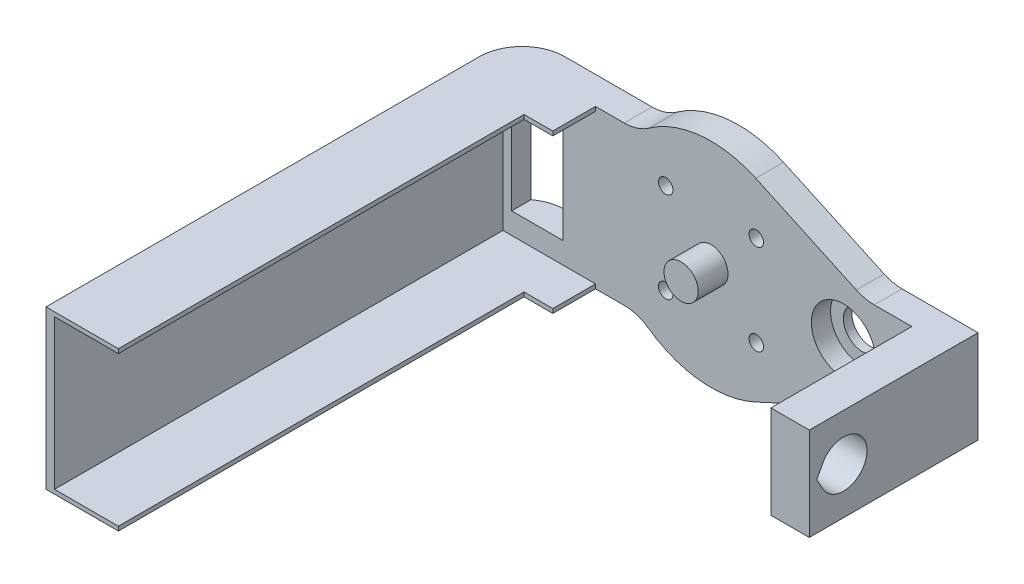
SolidWorks part; units mm, degrees
ref_plane "Front Plane" through (0, 0, 0) normal (0, 0, 1) x (1, 0, 0)
ref_plane "Top Plane" through (0, 0, 0) normal (0, 1, 0) x (1, 0, 0)
ref_plane "Right Plane" through (0, 0, 0) normal (1, 0, 0) x (0, 0, -1)
sketch "Sketch1" plane through (0, 0, 0) normal (0, 0, 1) x (1, 0, 0)
  line L0 (10.4839, 22.6956) -> (36.0323, 10.8939)
  line L1 (36.0323, -10.8939) -> (10.4839, -22.6956)
  circle A0 centre (0, 0) radius 22.215 construction
  circle A1 centre (31, 0) radius 10.2 construction
  arc A2 (10.4839, 22.6956) -> (10.4839, -22.6956) centre (0, 0) ccw
  arc A3 (36.0323, -10.8939) -> (36.0323, 10.8939) centre (31, 0) ccw
  dimension "D1" = 20.4
  dimension "D2" = 44.43
  dimension "D4" = 25
  dimension "D5" = 12
  dimension "D3" = 31
extrude "Boss-Extrude1" add sketch "Sketch1" along normal blind 4.5
sketch "Sketch2" plane through (0, 0, 4.5) normal (0, 0, 1) x (1, 0, 0)
  circle A0 centre (31, 0) radius 7.5
  dimension "D1" = 15
extrude "Cut-Extrude1" cut sketch "Sketch2" against normal through all
sketch "Sketch3" plane through (0, 0, 4.5) normal (0, 0, 1) x (1, 0, 0)
  circle A0 centre (0, 0) radius 4
  dimension "D1" = 8
extrude "Boss-Extrude2" add sketch "Sketch3" along normal blind 7
sketch "Sketch4" plane through (0, 0, 0) normal (0, 0, -1) x (-1, 0, 0)
  line L0 (-36.0323, 10.8939) -> (-56.0323, 10.8939)
  line L1 (-36.0323, -10.8939) -> (-56.0323, -10.8939)
  line L2 (-56.0323, -10.8939) -> (-56.0323, 10.8939)
  line L3 (22.5016, 10.8939) -> (42.5016, 10.8939)
  line L4 (42.5016, 10.8939) -> (42.5016, -10.8939)
  line L5 (42.5016, -10.8939) -> (22.5016, -10.8939)
  arc A0 (-10.4839, -22.6956) -> (-10.4839, 22.6956) centre (0, 0) ccw construction
  arc A1 (22.5016, -10.8939) -> (22.5016, 10.8939) centre (0, 0) ccw
  arc A2 (-36.0323, 10.8939) -> (-36.0323, -10.8939) centre (-31, 0) ccw construction
  arc A3 (-36.0323, 10.8939) -> (-36.0323, -10.8939) centre (-31, 0) ccw
  dimension "D1" = 20
  dimension "D2" = 20
extrude "Boss-Extrude3" add sketch "Sketch4" against normal up to surface (4.5 mm away) up to face at (4, 0, 4.5)
fillet "Fillet1" radius 10 4 edges at (-42.5016, 10.8939, 2.25) (-42.5016, -10.8939, 2.25) (56.0323, -10.8939, 2.25) (56.0323, 10.8939, 2.25)
sketch "Sketch8" plane through (0, 0, 4.5) normal (0, 0, 1) x (1, 0, 0)
  line L0 (56.0323, 0.8939) -> (56.0323, -0.8939) construction
  line L2 (56.0323, 0.8939) -> (56.0323, -0.8939)
  line L3 (55.4014, -4.3896) -> (55.4014, 4.3896)
  line L4 (-42.5016, -0.8939) -> (-42.5016, 0.8939) construction
  line L6 (-42.5016, -0.8939) -> (-42.5016, 0.8939)
  line L7 (-41.8707, 4.3896) -> (-41.8707, -4.3896)
  arc A0 (56.0323, 0.8939) -> (46.0323, 10.8939) centre (46.0323, 0.8939) ccw construction
  arc A1 (46.0323, -10.8939) -> (56.0323, -0.8939) centre (46.0323, -0.8939) ccw construction
  arc A2 (56.0323, 0.8939) -> (55.4014, 4.3896) centre (46.0323, 0.8939) ccw
  arc A3 (55.4014, -4.3896) -> (56.0323, -0.8939) centre (46.0323, -0.8939) ccw
  arc A4 (-32.5016, 10.8939) -> (-42.5016, 0.8939) centre (-32.5016, 0.8939) ccw construction
  arc A5 (-42.5016, -0.8939) -> (-32.5016, -10.8939) centre (-32.5016, -0.8939) ccw construction
  arc A6 (-41.8707, 4.3896) -> (-42.5016, 0.8939) centre (-32.5016, 0.8939) ccw
  arc A7 (-42.5016, -0.8939) -> (-41.8707, -4.3896) centre (-32.5016, -0.8939) ccw
extrude "Cut-Extrude4" cut sketch "Sketch8" against normal through all
sketch "Sketch9" plane through (0, 0, 4.5) normal (0, 0, 1) x (1, 0, 0)
  circle A0 centre (0, 0) radius 15 construction
  circle A1 centre (-10.6066, 10.6066) radius 1
  circle A2 centre (10.6066, 10.6066) radius 1
  circle A3 centre (10.6066, -10.6066) radius 1
  circle A4 centre (-10.6066, -10.6066) radius 1
  point P14 (0, 0)
  dimension "D1" = 30
  dimension "D2" = 2
  dimension "D3" = 4
extrude "Cut-Extrude5" cut sketch "Sketch9" against normal through all
sketch "Sketch10" plane through (0, 0, 4.5) normal (0, 0, 1) x (1, 0, 0)
  circle A0 centre (-10.6066, 10.6066) radius 1.7
  circle A1 centre (10.6066, 10.6066) radius 1.7
  circle A2 centre (10.6066, -10.6066) radius 1.7
  circle A3 centre (-10.6066, -10.6066) radius 1.7
  dimension "D1" = 3.4
extrude "Cut-Extrude6" cut sketch "Sketch10" against normal blind 2.4
sketch "Sketch11" plane through (0, 0, 0) normal (0, 0, -1) x (-1, 0, 0)
  line L0 (-40.9602, 14.6461) -> (-73.6718, 18.9155)
  line L1 (-73.6718, 18.9155) -> (-68.6403, -15.6759)
  line L2 (-68.6403, -15.6759) -> (-41.445, -13.2122)
  arc A0 (-40.9602, 14.6461) -> (-41.445, -13.2122) centre (0, 0) ccw
  dimension "D1" = 87
extrude "Cut-Extrude7" cut sketch "Sketch11" against normal up to surface (4.5 mm away) up to face at (-8.9066, -10.6066, 4.5)
fillet "Fillet2" radius 10 2 edges at (42.1138, -10.8939, 2.25) (42.1138, 10.8939, 2.25)
sketch "Sketch12" plane through (0, 0, 4.5) normal (0, 0, 1) x (1, 0, 0)
  line L0 (-22.5016, 10.8939) -> (-42.5927, 14.8195)
  line L1 (-42.5927, 14.8195) -> (-48.1481, -13.6126)
  line L2 (-48.1481, -13.6126) -> (-27.4273, -14.3153)
  line L3 (-27.4273, -14.3153) -> (-22.5016, -10.8939)
  arc A0 (-22.5016, 10.8939) -> (-22.5016, -10.8939) centre (0, 0) ccw
extrude "Cut-Extrude8" cut sketch "Sketch12" against normal through all
sketch "Sketch23" plane through (0, 0, 0) normal (0, 0, -1) x (-1, 0, 0)
  line L2 (-36.0323, -10.8939) -> (-10.4839, -22.6956)
  line L3 (-10.4839, 22.6956) -> (-36.0323, 10.8939)
  line L4 (-36.0323, -10.8939) -> (-10.4839, -22.6956)
  line L5 (-10.4839, 22.6956) -> (-36.0323, 10.8939)
  circle A0 centre (-10.6066, -10.6066) radius 1 construction
  circle A1 centre (10.6066, -10.6066) radius 1 construction
  circle A2 centre (10.6066, 10.6066) radius 1 construction
  circle A3 centre (-10.6066, 10.6066) radius 1 construction
  arc A4 (-10.4839, -22.6956) -> (-10.4839, 22.6956) centre (0, 0) ccw
  arc A5 (-36.0323, 10.8939) -> (-43.4709, 1.5916) centre (-33.4776, 1.2257) ccw
  arc A6 (-43.4709, 1.5916) -> (-43.4709, -1.5916) centre (0, 0) ccw
  arc A7 (-43.4709, -1.5916) -> (-36.0323, -10.8939) centre (-33.4776, -1.2257) ccw
  arc A8 (-10.4839, -22.6956) -> (-10.4839, 22.6956) centre (0, 0) ccw
  arc A9 (-36.0323, 10.8939) -> (-43.4709, 1.5916) centre (-33.4776, 1.2257) ccw
  arc A10 (-43.4709, 1.5916) -> (-43.4709, -1.5916) centre (0, 0) ccw
  arc A11 (-43.4709, -1.5916) -> (-36.0323, -10.8939) centre (-33.4776, -1.2257) ccw
  circle A12 centre (-10.6066, -10.6066) radius 1
  circle A13 centre (10.6066, -10.6066) radius 1
  circle A14 centre (10.6066, 10.6066) radius 1
  circle A15 centre (-10.6066, 10.6066) radius 1
  circle A16 centre (-31, 0) radius 4.5
  dimension "D2" = 9
  dimension "D1" = 0
extrude "Boss-Extrude6" add sketch "Sketch23" along normal blind 2
sketch "Sketch24" plane through (0, 0, -2) normal (0, 0, -1) x (-1, 0, 0)
  line L0 (-10.6066, 10.6066) -> (10.6066, 10.6066) construction
ref_axis "Axis1" through (10.6066, 10.6066, -2) along (-1, 0, 0)
sketch "Sketch25" plane through (0, 0, -2) normal (0, 0, -1) x (-1, 0, 0)
  line L1 (-36.0323, 10.8939) -> (-56.0323, 10.8939)
  line L3 (-36.0323, -10.8939) -> (-56.0323, -10.8939)
  line L4 (-56.0323, 10.8939) -> (-56.0323, -10.8939)
  arc A0 (-43.4709, -1.5916) -> (-36.0323, -10.8939) centre (-33.4776, -1.2257) ccw construction
  arc A1 (-43.4709, 1.5916) -> (-43.4709, -1.5916) centre (0, 0) ccw construction
  arc A2 (-36.0323, 10.8939) -> (-43.4709, 1.5916) centre (-33.4776, 1.2257) ccw construction
  arc A3 (-43.4709, -1.5916) -> (-36.0323, -10.8939) centre (-33.4776, -1.2257) ccw
  arc A4 (-43.4709, 1.5916) -> (-43.4709, -1.5916) centre (0, 0) ccw
  arc A5 (-36.0323, 10.8939) -> (-43.4709, 1.5916) centre (-33.4776, 1.2257) ccw
  dimension "D1" = 20
extrude "Boss-Extrude7" add sketch "Sketch25" against normal up to surface (6.5 mm away) up to face at (24.5985, 0, 4.5)
sketch "Sketch26" plane through (0, 0, 4.5) normal (0, 0, 1) x (1, 0, 0)
  line L0 (36.0323, 10.8939) -> (56.0323, 10.8939) construction
  line L1 (56.0323, -10.8939) -> (47.0323, -10.8939)
  line L2 (56.0323, -10.8939) -> (56.0323, 10.8939)
  line L3 (56.0323, 10.8939) -> (47.0323, 10.8939)
  line L4 (47.0323, -10.8939) -> (47.0323, 10.8939)
  dimension "D1" = 9
extrude "Boss-Extrude8" add sketch "Sketch26" along normal blind 33
sketch "Sketch27" plane through (56.0323, 0, 0) normal (1, 0, 0) x (0, 0, -1)
  circle A0 centre (-29.5, 0) radius 5
extrude "Cut-Extrude9" cut sketch "Sketch27" against normal up to next
sketch "Sketch28" plane through (0, 0, -2) normal (0, 0, -1) x (-1, 0, 0)
  line L1 (16.8152, 18.5) -> (50.7321, 18.5)
  line L3 (16.8152, -18.5) -> (50.7321, -18.5)
  line L4 (0, 0) -> (54, 0) construction
  line L5 (54, 0) -> (25.875, 18.5) construction
  line L6 (54, 0) -> (31.6196, -18.5) construction
  line L7 (50.7321, -18.5) -> (25, 0) construction
  line L8 (25, 0) -> (50.7321, 18.5) construction
  line L9 (50.7321, 18.5) -> (50.7321, -18.5)
  arc A0 (50.7321, -18.5) -> (50.7321, 18.5) centre (0, 0) ccw construction
  arc A2 (-10.4839, -22.6956) -> (-10.4839, 22.6956) centre (0, 0) ccw construction
  arc A3 (16.8152, -18.5) -> (16.8152, 18.5) centre (0, 0) ccw
  dimension "D1" = 108
  dimension "D3" = 37
extrude "Boss-Extrude9" add sketch "Sketch28" against normal up to surface (6.5 mm away) up to face at (38.5, 0, 4.5)
sketch "Sketch29" plane through (0, 0, 4.5) normal (0, 0, 1) x (1, 0, 0)
  line L0 (-50.7321, 18.5) -> (-33.7737, 18.5)
  line L1 (-50.7321, 18.5) -> (-50.7321, -18.5)
  line L2 (-50.7321, -18.5) -> (-33.7737, -18.5)
  line L3 (-16.8152, -18.5) -> (-50.7321, -18.5) construction
  line L4 (-50.7321, 18.5) -> (-16.8152, 18.5) construction
  line L5 (-48.7321, 16.5) -> (-48.7321, -16.5)
  line L6 (-48.7321, 16.5) -> (-50.7321, 18.5) construction
  line L7 (-48.7321, -16.5) -> (-50.7321, -18.5) construction
  line L8 (-48.7321, 16.5) -> (-33.7737, 16.5)
  line L9 (-33.7737, 16.5) -> (-33.7737, 18.5)
  line L10 (-33.7737, -18.5) -> (-33.7737, -16.5)
  line L11 (-33.7737, -16.5) -> (-48.7321, -16.5)
  dimension "D1" = 33
  dimension "D2" = 2
extrude "Boss-Extrude10" add sketch "Sketch29" along normal blind 105
fillet "Fillet3" radius 10 1 edges at (-50.7321, 0, -2)
fillet "Fillet4" radius 10 4 edges at (36.0323, 10.8939, 1.25) (36.0323, -10.8939, 1.25) (-16.8152, 18.5, 1.25) (-16.8152, -18.5, 1.25)
sketch "Sketch30" plane through (56.0323, 0, 0) normal (1, 0, 0) x (0, 0, -1)
  line L0 (-34.1928, 1.7255) -> (-34.8273, 0)
  line L1 (-34.8273, 0) -> (-34.1928, -1.7255)
  line L2 (-34.5, 0) -> (-34.8273, 0) construction
  circle A0 centre (-29.5, 0) radius 5 construction
  arc A1 (-34.1928, 1.7255) -> (-34.1928, -1.7255) centre (-29.5, 0) ccw
extrude "Cut-Extrude10" cut sketch "Sketch30" against normal up to surface (9 mm away) up to face at (47.0323, 0, 24.5)
sketch "Sketch31" plane through (0, 0, 4.5) normal (0, 0, 1) x (1, 0, 0)
  line L0 (-46.6706, 12.5) -> (-48.7321, 16.5) construction
  line L1 (-46.6706, 12.5) -> (-34.6706, 12.5)
  line L2 (-46.6706, 12.5) -> (-46.6706, -12.5)
  line L3 (-46.6706, -12.5) -> (-34.6706, -12.5)
  line L4 (-34.6706, 12.5) -> (-34.6706, -12.5)
  line L5 (-46.6706, -12.5) -> (-48.7321, -16.5) construction
  dimension "D1" = 25
  dimension "D2" = 12
  dimension "D3" = 4.5
extrude "Cut-Extrude11" cut sketch "Sketch31" against normal through all
sketch "Sketch32" plane through (0, 0, 4.5) normal (0, 0, 1) x (1, 0, 0)
  line L0 (-33.7737, 18.5) -> (-33.7737, 16.5)
  line L1 (-33.7737, 16.5) -> (-27.7321, 16.5)
  line L2 (-27.7321, 16.5) -> (-27.7321, -16.5)
  line L3 (-27.7321, -16.5) -> (-33.7737, -16.5)
  line L4 (-33.7737, -16.5) -> (-33.7737, -18.5)
  line L5 (-33.7737, -18.5) -> (-27.045, -18.5)
  line L6 (-20.3162, -18.5) -> (-33.7737, -18.5) construction
  line L7 (-27.045, -18.5) -> (-27.045, 18.5)
  line L8 (-33.7737, 18.5) -> (-20.3162, 18.5) construction
  line L9 (-27.045, 18.5) -> (-33.7737, 18.5)
extrude "Boss-Extrude11" add sketch "Sketch32" along normal blind 10
sketch "Sketch33" plane through (-27.045, 0, 0) normal (1, 0, 0) x (0, 0, -1)
  line L0 (-4.5, -22.6956) -> (-4.5, -11.8156) construction
  line L1 (-14.5, 16.5) -> (-4.5, 16.5)
  line L2 (-14.5, 16.5) -> (-14.5, -16.5)
  line L3 (-14.5, -16.5) -> (-4.5, -16.5)
  line L4 (-4.5, 16.5) -> (-4.5, -16.5)
  line L5 (-109.5, -16.5) -> (-4.5, -16.5) construction
extrude "Cut-Extrude12" cut sketch "Sketch33" against normal up to next
sketch "Sketch34" plane through (-48.7321, 0, 0) normal (1, 0, 0) x (0, 0, -1)
  line L0 (-109.5, 16.5) -> (-109.5, 18.5) construction
  line L1 (-109.5, 17.5) -> (-4.5, 17.5)
  line L2 (-109.5, 17.5) -> (-109.5, -17.5)
  line L3 (-109.5, -17.5) -> (-4.5, -17.5)
  line L4 (-4.5, 17.5) -> (-4.5, -17.5)
  line L5 (-4.5, -18.5) -> (-4.5, -16.5) construction
extrude "Cut-Extrude13" cut sketch "Sketch34" along normal up to surface (21.6872 mm away) up to face at (-27.045, 17.5, 9.5)
sketch "Sketch35" plane through (56.0323, 0, 0) normal (1, 0, 0) x (0, 0, -1)
  circle A0 centre (-29.5, 0) radius 5.5
  dimension "D1" = 11
extrude "Cut-Extrude14" cut sketch "Sketch35" against normal up to next
sketch "Sketch36" plane through (56.0323, 0, 0) normal (1, 0, 0) x (0, 0, -1)
  line L0 (-34.3284, 2.6337) -> (-35.765, 0)
  line L1 (-35.765, 0) -> (-34.3284, -2.6337)
  line L2 (-35.765, 0) -> (0, 0) construction
  circle A0 centre (-29.5, 0) radius 5.5 construction
  arc A1 (-34.3284, -2.6337) -> (-34.3284, 2.6337) centre (-29.5, 0) cw
  dimension "D1" = 3
extrude "Cut-Extrude15" cut sketch "Sketch36" against normal up to next
